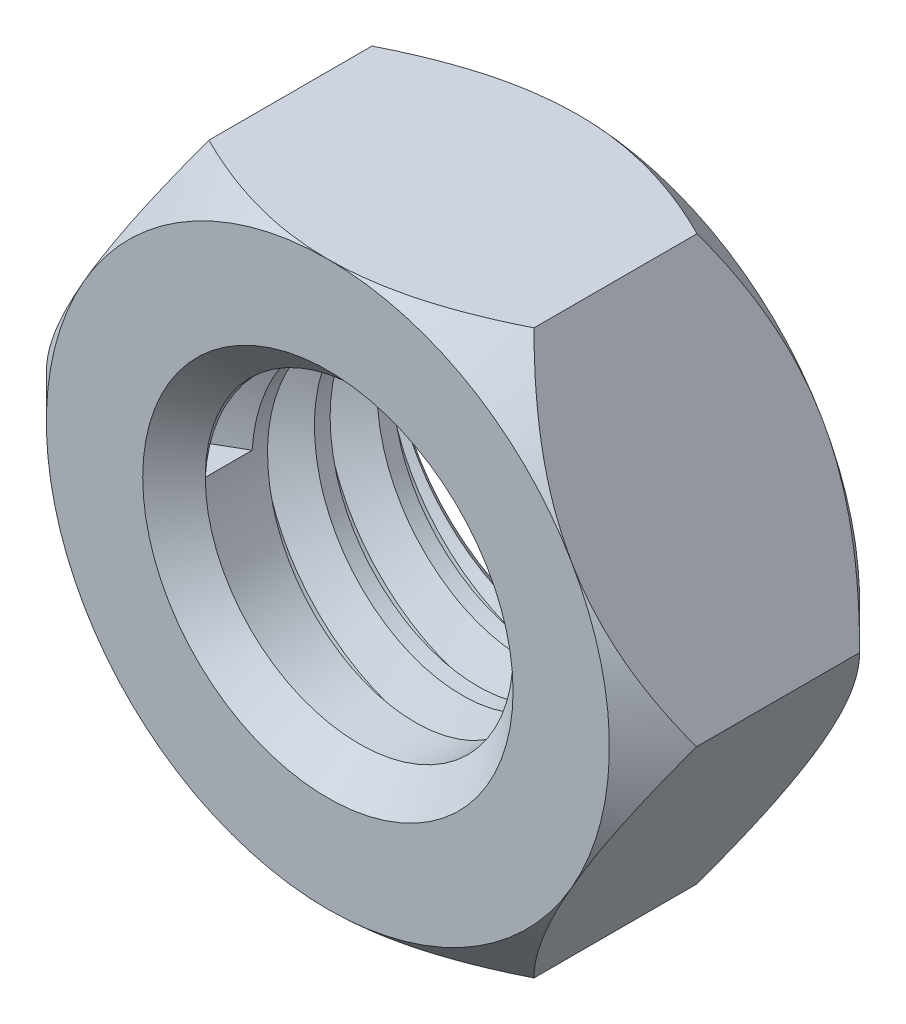
SolidWorks part; units mm, degrees
ref_plane "Front Plane" through (0, 0, 0) normal (0, 0, 1) x (1, 0, 0)
ref_plane "Top Plane" through (0, 0, 0) normal (0, 1, 0) x (1, 0, 0)
ref_plane "Right Plane" through (0, 0, 0) normal (1, 0, 0) x (0, 0, -1)
sketch "Sketch1" plane through (0, 0, 0) normal (0, 0, 1) x (1, 0, 0)
  line L1 (2.5981, 4.5) -> (-2.5981, 4.5)
  line L2 (-2.5981, 4.5) -> (-5.1962, 0)
  line L3 (-5.1962, 0) -> (-2.5981, -4.5)
  line L4 (-2.5981, -4.5) -> (2.5981, -4.5)
  line L5 (2.5981, -4.5) -> (5.1962, 0)
  line L6 (5.1962, 0) -> (2.5981, 4.5)
  circle A0 centre (0, 0) radius 4.5 construction
  dimension "D1" = 9
extrude "Boss-Extrude1" add sketch "Sketch1" along normal mid plane 4
sketch "Sketch2" plane through (0, 0, 2) normal (0, 0, 1) x (1, 0, 0)
  line L0 (2.5981, 4.5) -> (-2.5981, 4.5) construction
  circle A0 centre (0, 0) radius 4.5
extrude "Cut-Extrude1" cut sketch "Sketch2" against normal through all draft 45 flip side to cut
mirror "Mirror1" about plane through (0, 0, 0) normal (0, 0, 1) of "Cut-Extrude1"
sketch "Sketch3" plane through (0, 0, 2) normal (0, 0, 1) x (1, 0, 0)
  circle A0 centre (0, 0) radius 2.46
  dimension "D1" = 4.92
extrude "Cut-Extrude2" cut sketch "Sketch3" against normal through all
chamfer "Chamfer1" distance 0.5 angle 45 2 edges at (2.46, 0, 2) (2.46, 0, -2)
thread "Thread1" pitch 1 method cut profile "Thread Profile1" start angle 0, offset 0, length 0, pitch 1, diameter 4.92
ref_plane "Plane1" through (-2.46, 0, 1.5) normal (0, -1, 0) x (-1, 0, 0)
sketch "Thread Profile1" plane through (-2.46, 0, 1.5) normal (0, -1, 0) x (-1, 0, 0)
  line L0 (0, 0) -> (0, 1) construction
  line L1 (0, 0) -> (0.5413, 0.3125)
  line L2 (0.5413, 0.3125) -> (0.5413, 0.4375)
  line L3 (0.5413, 0.4375) -> (0, 0.75)
  line L4 (0.5413, 0.375) -> (0, 0.375) construction
  line L11 (0, 0) -> (0, 0.75)
  point P2 (0, 0)
  dimension "Pitch" = 1
  dimension "Profile_Angle" = 60
  dimension "Profile_Land" = 0.125
  dimension "Profile_Height" = 0.5413
